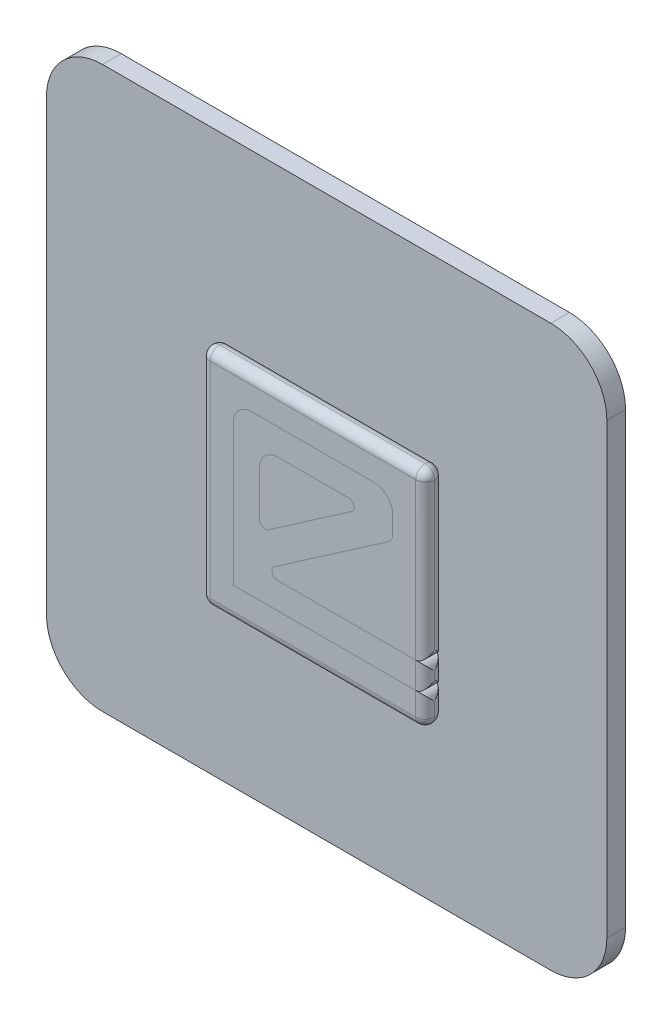
SolidWorks part; units mm, degrees
note: The reader was unsure of these and kept them because the rebuilt part matched: shared geometry of "Sketch2<3>".
ref_plane "Front Plane" through (0, 0, 0) normal (0, 0, 1) x (1, 0, 0)
ref_plane "Top Plane" through (0, 0, 0) normal (0, 1, 0) x (1, 0, 0)
ref_plane "Right Plane" through (0, 0, 0) normal (1, 0, 0) x (0, 0, -1)
sketch "Sketch1" plane through (0, 0, 0) normal (0, 0, 1) x (1, 0, 0)
  line L1 (30, 0) -> (270, 0)
  line L2 (0, 30) -> (0, 270)
  line L3 (30, 300) -> (270, 300)
  line L4 (300, 30) -> (300, 270)
  arc A0 (30, 0) -> (0, 30) centre (30, 30) cw
  arc A1 (270, 0) -> (300, 30) centre (270, 30) ccw
  arc A2 (270, 300) -> (300, 270) centre (270, 270) cw
  arc A3 (0, 270) -> (30, 300) centre (30, 270) cw
  point P7 (0, 0)
  point P10 (300, 0)
  point P13 (300, 300)
  point P16 (0, 300)
  dimension "D3" = 30
  dimension "D1" = 300
  dimension "D2" = 300
extrude "Boss-Extrude1" add sketch "Sketch1" along normal blind 10
sketch "Sketch2" plane through (0, 0, 10) normal (0, 0, 1) x (1, 0, 0)
  line L0 (212.6833, 103.605) -> (110.0174, 103.605)
  line L1 (92.6833, 86.2708) -> (212.6833, 86.2708)
  line L2 (92.6833, 86.2708) -> (92.6833, 206.2708)
  line L3 (92.6833, 206.2708) -> (212.6833, 206.2708)
  line L4 (212.6833, 86.2708) -> (212.6833, 206.2708)
  line L5 (92.6833, 86.2708) -> (212.6833, 206.2708) construction
  line L6 (92.6833, 206.2708) -> (212.6833, 86.2708) construction
  line L7 (110.0174, 103.605) -> (110.0174, 178.9366)
  line L8 (120.0174, 188.9366) -> (185.3491, 188.9366)
  line L9 (195.3491, 178.9366) -> (195.3491, 169.5004)
  line L10 (193.1903, 165.3861) -> (131.9745, 123.1118)
  line L11 (133.6793, 117.6432) -> (212.6833, 117.6432)
  line L12 (124.0557, 141.0768) -> (124.0557, 164.8984)
  line L13 (134.0557, 174.8984) -> (171.6873, 174.8984)
  line L14 (173.392, 169.4298) -> (128.7604, 138.6083)
  arc A0 (171.6873, 174.8984) -> (173.392, 169.4298) centre (171.6873, 171.8984) cw
  arc A1 (124.0557, 164.8984) -> (134.0557, 174.8984) centre (134.0557, 164.8984) cw
  arc A2 (110.0174, 178.9366) -> (120.0174, 188.9366) centre (120.0174, 178.9366) cw
  arc A3 (185.3491, 188.9366) -> (195.3491, 178.9366) centre (185.3491, 178.9366) cw
  arc A4 (131.9745, 123.1118) -> (133.6793, 117.6432) centre (133.6793, 120.6432) ccw
  arc A5 (124.0557, 141.0768) -> (128.7604, 138.6083) centre (127.0557, 141.0768) ccw
  arc A6 (195.3491, 169.5004) -> (193.1903, 165.3861) centre (190.3491, 169.5004) cw
  point P0 (152.6833, 146.2708)
  point P17 (181.3108, 174.8984)
  point P20 (124.0557, 174.8984)
  point P23 (110.0174, 188.9366)
  point P26 (195.3491, 188.9366)
  point P29 (124.0557, 117.6432)
  dimension "D4" = 3
  dimension "D5" = 10
  dimension "D6" = 10
  dimension "D3" = 3
  dimension "D7" = 3
  dimension "D8" = 5
  dimension "D1" = 120
  dimension "D2" = 120
extrude "Boss-Extrude2" add sketch "Sketch2" along normal blind 10 separate body contours L10 A4 L11 L4 L3 L2 L1 L0 L7 A2 L8 A3 L9 | A1 L12 L14 A0 L13
extrude "Boss-Extrude3" add sketch "Sketch2<3>" along normal blind 10 separate body contours A4 L10 L9 A3 L8 A2 L7 L0 L4 L11 L12 A1 L13 A0 L14
sketch "Sketch2<3>" plane through (0, 0, 10) normal (0, 0, 1) x (1, 0, 0) same geometry as "Sketch2"
fillet "Fillet1" radius 5 12 edges at (152.6833, 86.2708, 20) (152.6833, 86.2708, 10) (212.6833, 94.9379, 20) (212.6833, 103.605, 15) (212.6833, 94.9379, 10) (212.6833, 117.6432, 15) (212.6833, 161.957, 20) (212.6833, 161.957, 10) (152.6833, 206.2708, 20) (152.6833, 206.2708, 10) (92.6833, 146.2708, 20) (92.6833, 146.2708, 10)
fillet "Fillet2" radius 5 4 edges at (212.6833, 103.605, 15) (212.6833, 110.6241, 20) (212.6833, 117.6432, 15) (212.6833, 110.6241, 10)
